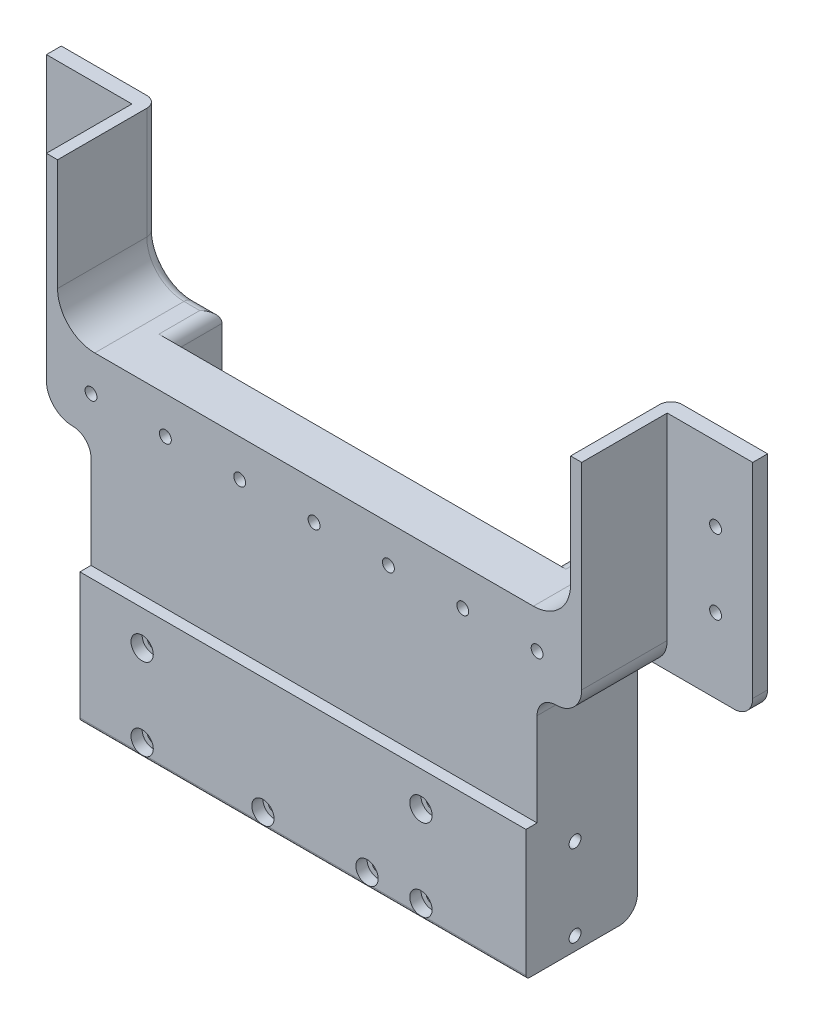
SolidWorks part; units mm, degrees
ref_plane "前视基准面" through (0, 0, 0) normal (0, 0, 1) x (1, 0, 0)
ref_plane "上视基准面" through (0, 0, 0) normal (0, 1, 0) x (1, 0, 0)
ref_plane "右视基准面" through (0, 0, 0) normal (1, 0, 0) x (0, 0, -1)
other "Configuration Table"
sketch "草图1" plane through (0, 0, 0) normal (0, 1, 0) x (1, 0, 0)
  line L1 (-75, -10) -> (75, -10)
  line L2 (-75, -10) -> (-75, 10)
  line L3 (-75, 10) -> (75, 10)
  line L4 (75, -10) -> (75, 10)
  line L5 (-75, -10) -> (75, 10) construction
  line L6 (-75, 10) -> (75, -10) construction
  point P0 (0, 0)
  dimension "D1" = 20
  dimension "D2" = 150
extrude "凸台-拉伸1" add sketch "草图1" along normal blind 20
sketch "草图2" plane through (0, 0, 10) normal (0, 0, 1) x (1, 0, 0)
  line L0 (-75, 0) -> (75, 0) construction
  line L1 (0, 0) -> (60, 0)
  line L2 (0, 0) -> (0, -65)
  line L3 (0, -65) -> (60, -65)
  line L4 (60, 0) -> (60, -65)
  line L6 (0, 0) -> (-60, 0)
  line L7 (0, 0) -> (0, -65)
  line L8 (0, -65) -> (-60, -65)
  line L9 (-60, 0) -> (-60, -65)
  line M1 (-75, 0) -> (75, 0)
  dimension "D1" = 65
  dimension "D2" = 60
  dimension "D3" = 65
  dimension "D4" = 60
extrude "凸台-拉伸2" add sketch "草图2" against normal blind 5 contours L9 L8 L2 M1 | L4 L2 L3 M1 region at (30, -32.5, 10) region at (-30, -32.5, 10)
sketch "草图3" plane through (0, 0, -10) normal (0, 0, -1) x (-1, 0, 0)
  line L0 (-75, 20) -> (75, 20) construction
  circle A0 centre (0, 10) radius 1.6
  dimension "D1" = 3.2
  dimension "D2" = 10
extrude "切除-拉伸1" cut sketch "草图3" against normal blind 25
sketch "草图4" plane through (0, 20, 0) normal (0, 1, 0) x (1, 0, 0)
  line L0 (28.95, 3) -> (-41.25, 3) construction
  line L1 (0, 3) -> (51.75, 3)
  line L2 (0, 3) -> (0, 17.96)
  line L3 (0, 17.96) -> (51.75, 17.96)
  line L4 (51.75, 3) -> (51.75, 17.96)
  line L5 (51.75, -1.3) -> (51.75, 46.7) construction
  line L7 (0, 3) -> (-51.75, 3)
  line L8 (0, 3) -> (0, 19.54)
  line L9 (0, 19.54) -> (-51.75, 19.54)
  line L10 (-51.75, 3) -> (-51.75, 19.54)
  line L11 (-51.75, 5.7) -> (-51.75, 39.7001) construction
  line M6 (75, 10) -> (-75, 10)
  dimension "D1" = 14.96
  dimension "D2" = 51.75
  dimension "D3" = 16.54
  dimension "D4" = 51.75
extrude "切除-拉伸2" cut sketch "草图4" against normal blind 27 contours L10 L7 L2 M6 | L1 L4 L2 M6 region at (25.875, 20, -6.5) region at (-25.875, 20, -6.5)
sketch "草图5" plane through (0, 0, 5) normal (0, 0, -1) x (-1, 0, 0)
  circle A0 centre (43.25, -61.3707) radius 1.6
  circle A1 centre (43.25, -39.3707) radius 1.6
  circle A2 centre (10.75, -61.3707) radius 1.6
  circle A3 centre (-17.25, -61.3707) radius 1.6
  circle A4 centre (-31.75, -61.3707) radius 1.6
  circle A5 centre (-31.75, -39.3707) radius 1.6
  dimension "D1" = 3.2
  dimension "D2" = 3.2
  dimension "D3" = 3.2
  dimension "D4" = 3.2
  dimension "D5" = 3.2
  dimension "D6" = 3.2
extrude "切除-拉伸3" cut sketch "草图5" against normal blind 27
sketch "草图6" plane through (0, 0, 5) normal (0, 0, -1) x (-1, 0, 0)
  line L1 (-51.75, 0) -> (51.75, 0)
  line L2 (-51.75, 0) -> (-51.75, -35)
  line L3 (-51.75, -35) -> (51.75, -35)
  line L4 (51.75, 0) -> (51.75, -35)
  dimension "D1" = 35
extrude "凸台-拉伸3" add sketch "草图6" along normal blind 8
sketch "草图7" plane through (0, 0, 10) normal (0, 0, 1) x (1, 0, 0)
  line L1 (60, -65) -> (-60, -65)
  line L2 (60, -65) -> (60, -30)
  line L3 (60, -30) -> (-60, -30)
  line L4 (-60, -65) -> (-60, -30)
  line L5 (-60, 0) -> (-60, -65) construction
  circle A0 centre (31.75, -39.3707) radius 3
  circle A1 centre (31.75, -61.3707) radius 3
  circle A2 centre (17.25, -61.3707) radius 3
  circle A3 centre (-10.75, -61.3707) radius 3
  circle A4 centre (-43.25, -39.3707) radius 3
  circle A5 centre (-43.25, -61.3707) radius 3
  dimension "D3" = 6
  dimension "D4" = 6
  dimension "D5" = 6
  dimension "D6" = 6
  dimension "D7" = 6
  dimension "D8" = 6
  dimension "D1" = 35
  dimension "D2" = 120
extrude "凸台-拉伸4" add sketch "草图7" along normal blind 3
sketch "草图8" plane through (0, 0, -10) normal (0, 0, -1) x (-1, 0, 0)
  line L0 (75, 20) -> (75, 0) construction
  line L1 (51.75, 20) -> (75, 20)
  line L2 (51.75, 20) -> (51.75, 0)
  line L3 (51.75, 0) -> (75, 0)
  line L4 (75, 20) -> (75, 0)
  line L6 (-75, 20) -> (-51.75, 20)
  line L7 (-75, 20) -> (-75, 0)
  line L8 (-75, 0) -> (-51.75, 0)
  line L9 (-51.75, 20) -> (-51.75, 0)
extrude "凸台-拉伸5" add sketch "草图8" along normal blind 3
pattern_linear "阵列(线性)1" count 5 spacing 20 along (1, 0, 0) count 6 spacing 20 along (-1, 0, 0) of "切除-拉伸1"
sketch "草图9" plane through (0, 0, -13) normal (0, 0, -1) x (-1, 0, 0)
  line L1 (-75, 0) -> (-95, 0)
  line L2 (-75, 20) -> (-75, 60)
  line L3 (-75, 60) -> (-95, 60)
  line L4 (-95, 0) -> (-95, 60)
  line L5 (75, 0) -> (95, 0)
  line L6 (75, 20) -> (75, 60)
  line L7 (75, 60) -> (95, 60)
  line L8 (95, 0) -> (95, 60)
  line L9 (-51.75, 0) -> (-75, 0)
  line L10 (-51.75, 0) -> (-51.75, 20)
  line L11 (-51.75, 20) -> (-75, 20)
  line L13 (51.75, 0) -> (75, 0)
  line L14 (51.75, 0) -> (51.75, 20)
  line L15 (51.75, 20) -> (75, 20)
  dimension "D1" = 60
  dimension "D2" = 20
  dimension "D3" = 60
  dimension "D4" = 20
extrude "凸台-拉伸6" add sketch "草图9" along normal blind 4
sketch "草图10" plane through (0, 20, 0) normal (0, 1, 0) x (1, 0, 0)
  line L1 (-75, -10) -> (-72, -10)
  line L2 (-75, -10) -> (-75, 13)
  line L3 (-75, 13) -> (-72, 13)
  line L4 (-72, -10) -> (-72, 13)
  line L5 (75, 13) -> (72, 13)
  line L6 (75, 13) -> (75, -10)
  line L7 (75, -10) -> (72, -10)
  line L8 (72, 13) -> (72, -10)
  line L9 (-75, -10) -> (75, -10) construction
  dimension "D1" = 23
  dimension "D2" = 3
  dimension "D3" = 23
  dimension "D4" = 3
extrude "切除-拉伸4" cut sketch "草图10" against normal blind 29
sketch "草图11" plane through (0, 20, 0) normal (0, 1, 0) x (1, 0, 0)
  line L1 (-75, 17) -> (-69, 17)
  line L2 (-75, 17) -> (-75, -10)
  line L3 (-75, -10) -> (-69, -10)
  line L4 (-69, 17) -> (-69, -10)
  line L5 (-72, -10) -> (72, -10) construction
  line L7 (75, 17) -> (69, 17)
  line L8 (75, 17) -> (75, -10)
  line L9 (75, -10) -> (69, -10)
  line L10 (69, 17) -> (69, -10)
  line M1 (-75, 17) -> (-75, 13)
  line M2 (-75, 13) -> (-72, 13)
  line M3 (-72, 13) -> (-72, -10)
  line M4 (-72, -10) -> (72, -10)
  line M5 (72, -10) -> (72, 13)
  line M6 (72, 13) -> (75, 13)
  line M7 (75, 13) -> (75, 17)
  line M8 (75, 17) -> (51.75, 17)
  line M12 (-51.75, 17) -> (-75, 17)
  dimension "D1" = 27
  dimension "D2" = 6
  dimension "D3" = 27
  dimension "D4" = 6
extrude "凸台-拉伸7" add sketch "草图11" along normal blind 40 contours L4 M12 M1 M2 M3 M4 | L10 M8 M4 M5 M6 M7 region at (70.8871, 20, -4.9839) region at (-70.8871, 20, -4.9839)
fillet "圆角1" radius 10 2 edges at (69, 20, -3.5) (-69, 20, -3.5)
fillet "圆角2" radius 3 8 edges at (55.375, 20, -17) (66.0711, 22.9289, -17) (-55.375, 20, -17) (-66.0711, 22.9289, -17) (69, 45, -17) (-69, 45, -17) (51.75, 20, -10) (-51.75, 20, -10)
sketch "草图16" plane through (51.75, 0, 0) normal (1, 0, 0) x (0, 0, -1)
  line L0 (17, 0) -> (13, 0) construction
  line L1 (-5, -65) -> (17, -65)
  line L2 (-5, -65) -> (-5, 0)
  line L3 (-5, 0) -> (17, 0)
  line L4 (17, -65) -> (17, 0)
  circle A0 centre (0.2, -39.3708) radius 1.6
  circle A1 centre (0.2, -61.3707) radius 1.6
  dimension "D1" = 3.2
  dimension "D2" = 3.2
extrude "凸台-拉伸9" add sketch "草图16" along normal up to surface (8.25 mm away) up to face at (60, -31.6667, 9.3333)
sketch "草图17" plane through (-51.75, 0, 0) normal (-1, 0, 0) x (0, 0, 1)
  line L0 (-17, 0) -> (-17, 60) construction
  line L1 (5, -65) -> (-17, -65)
  line L2 (5, -65) -> (5, 0)
  line L3 (5, 0) -> (-17, 0)
  line L4 (-17, -65) -> (-17, 0)
  line L5 (-17, -65) -> (-17, 17) construction
  circle A0 centre (-0.2, -61.3707) radius 1.6
  circle A1 centre (-0.2, -39.3707) radius 1.6
  dimension "D1" = 3.2
  dimension "D2" = 3.2
extrude "凸台-拉伸10" add sketch "草图17" along normal up to surface (8.25 mm away) up to face at (-60, -31.6667, 9.3333)
fillet "圆角4" radius 5 4 edges at (-95, 0, -15) (95, 0, -15) (60, 0, -3.5) (-60, 0, -3.5)
fillet "圆角5" radius 5 2 edges at (-55.875, -65, -17) (55.875, -65, -17)
fillet "圆角6" radius 1 1 edges at (0, -65, 13)
sketch "草图18" plane through (0, 0, -3) normal (0, 0, -1) x (-1, 0, 0)
  circle A1 centre (0, 10) radius 3
  circle A2 centre (20, 10) radius 3
  circle A3 centre (40, 10) radius 3
  circle A4 centre (-20, 10) radius 3
  circle A5 centre (-40, 10) radius 3
  dimension "D1" = 6
  dimension "D2" = 6
  dimension "D3" = 6
  dimension "D4" = 6
  dimension "D5" = 6
extrude "切除-拉伸6" cut sketch "草图18" against normal blind 5
fillet "圆角7" radius 5 1 edges at (0, -35, -3)
fillet "圆角8" radius 7 2 edges at (72, 0, -1.5) (-72, 0, -1.5)
sketch "草图19" plane through (0, 0, 13) normal (0, 0, 1) x (1, 0, 0)
  circle A0 centre (85, 40) radius 1.6
  circle A1 centre (85, 20) radius 1.6
  circle A2 centre (-85, 20) radius 1.6
  circle A3 centre (-85, 40) radius 1.6
  dimension "D1" = 3.2
  dimension "D2" = 3.2
  dimension "D3" = 3.2
  dimension "D4" = 3.2
extrude "切除-拉伸7" cut sketch "草图19" against normal blind 45
